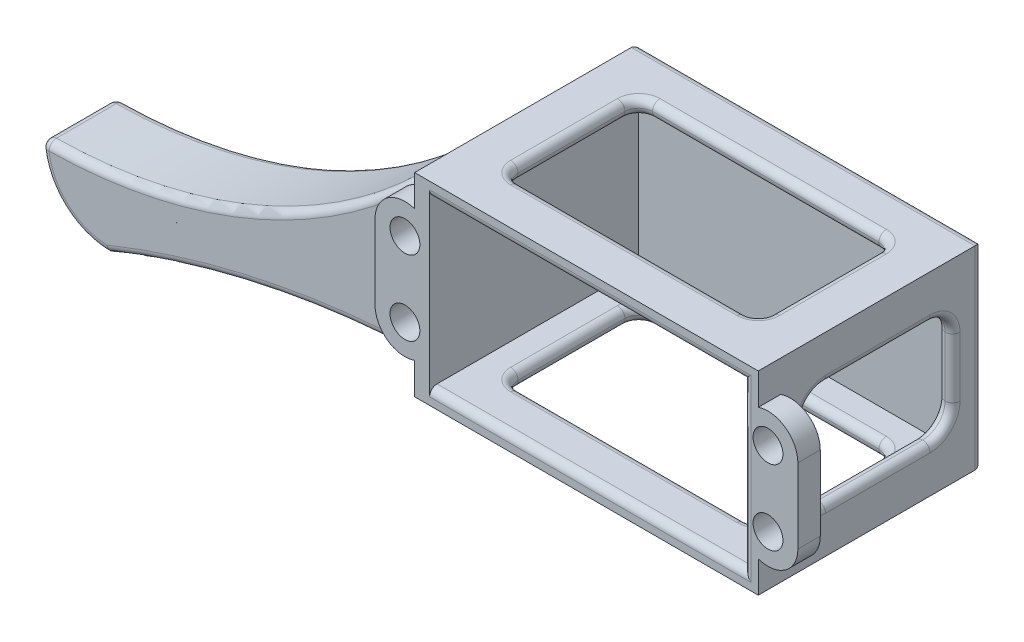
SolidWorks part; units mm, degrees
other "Markup1"
sketch "Sketch15" plane through (31.9332, 19.9963, 30) normal (0.1157, 0.1665, 0.9792) x (0.2474, -0.9596, 0.1339)
other "Markup2"
sketch "Sketch16" plane through (-78, 19.9963, 30) normal (-0.6723, 0.4833, 0.5608) x (0.1241, -0.6733, 0.7289)
material "Custom Plastic"
ref_plane "Front Plane" through (0, 0, 0) normal (0, 0, 1) x (1, 0, 0)
ref_plane "Top Plane" through (0, 0, 0) normal (0, 1, 0) x (1, 0, 0)
ref_plane "Right Plane" through (0, 0, 0) normal (1, 0, 0) x (0, 0, -1)
sketch "Sketch1" plane through (0, 0, 0) normal (0, 0, 1) x (1, 0, 0)
  line L0 (-23, 13) -> (-23, -13)
  line L1 (-20, 10) -> (20, 10) construction
  line L2 (-20, 10) -> (-20, -10) construction
  line L3 (-20, -10) -> (20, -10) construction
  line L4 (20, 10) -> (20, -10) construction
  line L5 (-20, 10) -> (20, -10) construction
  line L6 (-20, -10) -> (20, 10) construction
  line L7 (-23, -13) -> (23, -13)
  line L8 (23, 13) -> (23, -13)
  line L9 (-23, 13) -> (23, 13)
  point P0 (0, 0)
  dimension "D1" = 40
  dimension "D2" = 20
  dimension "D3" = 3
extrude "Boss-Extrude3" add sketch "Sketch1" along normal blind 30
shell "Shell1" thickness 2 removed face at (0, 0, 30)
sketch "Sketch2" plane through (0, 0, 30) normal (0, 0, 1) x (1, 0, 0)
  line L0 (0, 5) -> (0, -5) construction
  line L1 (-21, 11) -> (21, 11) construction
  line L2 (-21, 11) -> (-21, -11) construction
  line L3 (-21, -11) -> (21, -11) construction
  line L4 (21, 11) -> (21, -11) construction
  line L5 (-24.3, 5) -> (24.3, 5) construction
  line L6 (-24.3, 5) -> (-24.3, -5) construction
  line L7 (-24.3, -5) -> (24.3, -5) construction
  line L8 (24.3, 5) -> (24.3, -5) construction
  line L9 (-24.3, 5) -> (24.3, -5) construction
  line L10 (-24.3, -5) -> (24.3, 5) construction
  line L11 (-24.3, 0) -> (24.3, 0) construction
  line L13 (-28.3, 9) -> (28.3, 9)
  line L14 (-28.3, 9) -> (-28.3, -9)
  line L15 (-28.3, -9) -> (28.3, -9)
  line L16 (28.3, 9) -> (28.3, -9)
  line L17 (-28.3, 9) -> (28.3, -9) construction
  line L18 (-28.3, -9) -> (28.3, 9) construction
  circle A0 centre (-24.3, 5) radius 2
  circle A1 centre (24.3, 5) radius 2
  circle A2 centre (24.3, -5) radius 2
  circle A3 centre (-24.3, -5) radius 2
  circle A4 centre (-24.3, 5) radius 4
  circle A5 centre (-24.3, -5) radius 4
  circle A6 centre (24.3, 5) radius 4
  circle A7 centre (24.3, -5) radius 4
  point P6 (0, 0)
  point P28 (0, 0)
  line M7 (-23, 13) -> (-23, -13)
  line M9 (23, -13) -> (23, 13)
  dimension "D3" = 4
  dimension "D1" = 10
  dimension "D2" = 48.6
  dimension "D4" = 2
  dimension "D5" = 2
  dimension "D6" = 2
  dimension "D7" = 2
sketch "Sketch4" plane through (0, 0, 0) normal (0, 0, 1) x (1, 0, 0)
  line L0 (0, 5) -> (0, -5) construction
  line L1 (-20, 10) -> (20, 10) construction
  line L2 (-20, 10) -> (-20, -10) construction
  line L3 (-20, -10) -> (20, -10) construction
  line L4 (20, 10) -> (20, -10) construction
  line L5 (-24.3, 5) -> (24.3, 5) construction
  line L6 (-24.3, 5) -> (-24.3, -5) construction
  line L7 (-24.3, -5) -> (24.3, -5) construction
  line L8 (24.3, 5) -> (24.3, -5) construction
  line L9 (-24.3, 5) -> (24.3, -5) construction
  line L10 (-24.3, -5) -> (24.3, 5) construction
  line L11 (-24.3, 0) -> (24.3, 0) construction
  line L13 (-28.3, 9) -> (28.3, 9)
  line L14 (-28.3, 9) -> (-28.3, -9)
  line L15 (-28.3, -9) -> (28.3, -9)
  line L16 (28.3, 9) -> (28.3, -9)
  line L17 (-28.3, 9) -> (28.3, -9) construction
  line L18 (-28.3, -9) -> (28.3, 9) construction
  circle A0 centre (-24.3, 5) radius 2
  circle A1 centre (24.3, 5) radius 2
  circle A2 centre (24.3, -5) radius 2
  circle A3 centre (-24.3, -5) radius 2
  circle A4 centre (-24.3, 5) radius 4
  circle A5 centre (-24.3, -5) radius 4
  circle A6 centre (24.3, 5) radius 4
  circle A7 centre (24.3, -5) radius 4
  point P6 (0, 0)
  point P28 (0, 0)
  dimension "D3" = 4
  dimension "D1" = 10
  dimension "D2" = 48.6
  dimension "D4" = 2
  dimension "D5" = 2
  dimension "D6" = 2
  dimension "D7" = 2
extrude "Cut-Extrude2" cut sketch "Sketch4" along normal blind 17 from offset 25 contours A1 | A2 | A0 | A3 region at (-24.3, 5, 0) region at (24.3, 5, 0) region at (24.3, -5, 0) region at (-24.3, -5, 0)
extrude "Boss-Extrude4" add sketch "Sketch2" against normal blind 3 contours A6 A1 M9 | A7 L16 A6 M9 | A7 A2 M9 | A4 A0 M7 | L14 A5 A4 M7 | A5 A3 M7 region at (-23.6568, 8.8507, 30) region at (-26.3088, 0, 30) region at (-26.568, -1.8223, 30) region at (27.0606, 7.7606, 30) region at (26.3088, 0, 30) region at (27.0606, -7.7606, 30)
sketch "Sketch6" plane through (0, 13, 0) normal (0, 1, 0) x (1, 0, 0)
  line L0 (-23, -30) -> (-23, 0)
  line L1 (-23, 0) -> (23, 0)
  line L2 (23, 0) -> (23, -30)
  line L3 (23, -30) -> (23, 0) construction
  line L4 (23, -30) -> (-23, -30) construction
  line L5 (23, -30) -> (-23, -30)
  line L18 (17, -6) -> (-17, -6)
  line L19 (-17, -6) -> (-17, -24)
  line L20 (-17, -24) -> (17, -24)
  line L21 (17, -24) -> (17, -6)
  line L22 (15.1518, -6) -> (-15.1518, -6)
  line L23 (-17, -7.8482) -> (-17, -22.1518)
  line L24 (-15.1518, -24) -> (15.1518, -24)
  line L25 (17, -22.1518) -> (17, -7.8482)
  arc A0 (-15.1518, -6) -> (-17, -7.8482) centre (-15.1518, -7.8482) ccw
  arc A1 (-15.1518, -24) -> (-17, -22.1518) centre (-15.1518, -22.1518) cw
  arc A2 (15.1518, -24) -> (17, -22.1518) centre (15.1518, -22.1518) ccw
  arc A3 (17, -7.8482) -> (15.1518, -6) centre (15.1518, -7.8482) ccw
  dimension "D2" = 1.8482
  dimension "D1" = 6
sketch "Sketch9" plane through (0, 0, 0) normal (0, 0, 1) x (1, 0, 0)
  line L0 (0, 5) -> (0, -5) construction
  line L1 (-20, 10) -> (20, 10) construction
  line L2 (-20, 10) -> (-20, -10) construction
  line L3 (-20, -10) -> (20, -10) construction
  line L4 (20, 10) -> (20, -10) construction
  line L5 (-24.3, 5) -> (24.3, 5) construction
  line L6 (-24.3, 5) -> (-24.3, -5) construction
  line L7 (-24.3, -5) -> (24.3, -5) construction
  line L8 (24.3, 5) -> (24.3, -5) construction
  line L9 (-24.3, 5) -> (24.3, -5) construction
  line L10 (-24.3, -5) -> (24.3, 5) construction
  line L11 (-24.3, 0) -> (24.3, 0) construction
  line L12 (-24.3, 5) -> (-24.3, -5)
  line L13 (-28.3, 9) -> (28.3, 9)
  line L14 (-28.3, 9) -> (-28.3, -9)
  line L15 (-28.3, -9) -> (28.3, -9)
  line L16 (28.3, 9) -> (28.3, -9)
  line L17 (-28.3, 9) -> (28.3, -9) construction
  line L18 (-28.3, -9) -> (28.3, 9) construction
  line L19 (-24.3, 5) -> (10.5, 5)
  line L20 (-24.3, -5) -> (10.5, -5)
  line L21 (10.5, 5) -> (10.5, -5)
  circle A0 centre (-24.3, 5) radius 2
  circle A1 centre (24.3, 5) radius 2
  circle A2 centre (24.3, -5) radius 2
  circle A3 centre (-24.3, -5) radius 2
  circle A4 centre (-24.3, 5) radius 4
  circle A5 centre (-24.3, -5) radius 4
  circle A6 centre (24.3, 5) radius 4
  circle A7 centre (24.3, -5) radius 4
  circle A8 centre (10.5, 0) radius 4.5
  point P6 (0, 0)
  point P28 (0, 0)
  dimension "D3" = 4
  dimension "D9" = 9
  dimension "D1" = 10
  dimension "D2" = 48.6
  dimension "D8" = 34.8
  dimension "D4" = 2
  dimension "D5" = 2
  dimension "D6" = 2
  dimension "D7" = 2
extrude "Boss-Extrude16" add sketch "Sketch9" against normal blind 5 contours L21 A8 | L21 A8 region at (12.4099, 0, 0) region at (8.5901, 0, 0)
sketch "Sketch14" plane through (0, 0, 0) normal (0, 0, -1) x (-1, 0, 0)
  line L0 (69, 39) -> (69, -13)
  line L1 (-23, 13) -> (69, 13)
  line L2 (-23, 39) -> (-23, -13)
  line L3 (-23, -13) -> (69, -13) construction
  line L4 (23, 39) -> (23, -13)
  line L5 (-115, 39) -> (69, 39)
  line L6 (-69, 39) -> (-69, -65)
  line L7 (-23, 13) -> (-115, 13) construction
  line L8 (-115, 39) -> (-115, -65)
  line L9 (-23, -13) -> (-115, -13)
  line L10 (-23, -39) -> (-115, -39)
  line L11 (-23, -39) -> (161, -39)
  line L12 (23, -65) -> (23, -13)
  line L13 (-115, -65) -> (69, -65)
  line L14 (69, -65) -> (69, -13)
  line L15 (-23, -65) -> (-23, -13)
  line L16 (161, 13) -> (69, 13)
  line L17 (161, -13) -> (69, -13) construction
  line L18 (115, 39) -> (115, -13)
  line L19 (115, -65) -> (115, -13)
  line L20 (-14, 13) -> (-14, 22)
  line L21 (69, -13) -> (78, -13) construction
  line L22 (69, -13) -> (69, -22)
  line L23 (69, -22) -> (78, -22)
  line L24 (78, -13) -> (78, -22)
  line L25 (-14, 13) -> (-32, 13) construction
  line L26 (-23, 13) -> (-23, 22)
  line L27 (-14, 22) -> (-32, 22)
  line L28 (-32, 13) -> (-32, 22)
  line L30 (-23, 6.5199) -> (-32, 6.5199)
  line L31 (-23, 6.5199) -> (-23, 13)
  line L32 (-23, 13) -> (-32, 13)
  line L33 (-32, 6.5199) -> (-32, 13)
  line L34 (-23, 6.5199) -> (-21, 6.5199)
  line L35 (-23, 6.5199) -> (-23, 13)
  line L36 (-23, 13) -> (-21, 13)
  line L37 (-21, 6.5199) -> (-21, 13)
  arc A0 (23, -13) -> (69, -22) centre (23, -135.0556) cw
  arc A1 (69, -22) -> (78, -13) centre (69, -13) ccw
  arc A2 (78, -13) -> (23, 13) centre (78, 58.1731) cw
  arc A3 (-14, 13) -> (-30.0176, 19.6985) centre (-14, 35.5) cw
  arc A4 (-31.7134, 18.8176) -> (-29.7214, 13.2831) centre (-14.187, 22) ccw
  arc A5 (-31.9242, 7.6449) -> (-29.85, 12.125) centre (-23.6186, 6.5199) cw
  arc A6 (-23, 14.8784) -> (-30.8725, 6.5125) centre (-31.3814, 14.8784) cw
  arc A7 (-30.0176, 19.6985) -> (-31.7134, 18.8176) centre (-30.7295, 18.9963) ccw
  arc A8 (-29.85, 12.125) -> (-29.7214, 13.2831) centre (-30.5935, 12.7937) ccw
  arc A9 (-31.9242, 7.6449) -> (-30.8725, 6.5125) centre (-30.9332, 7.5106) ccw
  arc A10 (-29.7214, 13.2831) -> (-23, 6.5199) centre (-14.187, 22) ccw
  arc A11 (78, -16) -> (20.6817, 11.0959) centre (78, 58.1731) cw
  arc A12 (23, -10) -> (70.1306, -19.2212) centre (23, -135.0556) cw
  arc A13 (69, -19) -> (75, -13) centre (69, -13) ccw construction
  spline S0 degree 3 poles (59.5435, -15.4585) (63.9567, -16.6758) (61.1597, -13.9287) (59.5435, -13.667) knots 0 0 0 0 1 1 1 1
  point P9 (23, 13)
  point P18 (-69, -13)
  point P25 (69, -39)
  point P30 (78, -13)
  line M29 (23, -13) -> (23, 13)
  dimension "D5" = 1
  dimension "D1" = 55
  dimension "D2" = 9
  dimension "D3" = 9
  dimension "D4" = 9
  dimension "D6" = 2
  dimension "D7" = 3
extrude "Boss-Extrude18" add sketch "Sketch14" against normal blind 10 from offset 15 contours A12 A0 L14 M29 | S0 A12 L22 A11 | A1 A11 L22 L14 | A11 A1 A2 L0 L22 | S0 A11 L22 L0 A2 L4 | A12 S0 A11 L4 region at (-73.4109, -14.2953, 0) region at (-68.4591, -12.7143, 0) region at (-34.3258, -5.7975, 0) region at (-72.3453, -18.3731, 0) region at (-65.521, -16.1833, 0) region at (-46.2831, -14.4757, 0) offset against normal yes
extrude "Cut-Extrude5" cut sketch "Sketch6" against normal through all both and the other way through all contours A3 L25 A2 L24 A1 L23 A0 L22
fillet "Fillet50" radius 1 46 edges at (16.4587, 13, 6.5413) (17, 13, 15) (16.4587, 13, 23.4587) (0, 13, 24) (-16.4587, 13, 23.4587) (-17, 13, 15) (-16.4587, 13, 6.5413) (-16.4587, 11, 6.5413) (-17, 11, 15) (-16.4587, 11, 23.4587) (0, 11, 24) (16.4587, 11, 23.4587) (17, 11, 15) (16.4587, 11, 6.5413) (16.4587, -13, 6.5413) (17, -13, 15) (16.4587, -13, 23.4587) (0, -13, 24) (-16.4587, -13, 23.4587) (-17, -13, 15) (-16.4587, -13, 6.5413) (16.4587, -11, 6.5413) (17, -11, 15) (16.4587, -11, 23.4587) (0, -11, 24) (-16.4587, -11, 23.4587) (-17, -11, 15) (-16.4587, -11, 6.5413) (-23, 0, 0) (0, -13, 0) (23, 0, 0) (0, 13, 0) (0, 13, 6) (0, 11, 6) (0, -13, 6) (0, -11, 6) (-75.364, -19.364, 25) (-46.4361, -15.2711, 25) (-75.364, -19.364, 15) (-78, -13, 20) (-47.5821, -6.1725, 15) (-46.4361, -15.2711, 15) (-47.5821, -6.1725, 25) (0, -11, 30) (0, 11, 30) (21, 0, 30)
sketch "Sketch17" plane through (23, 0, 0) normal (1, 0, 0) x (0, 0, -1)
  line L0 (-24, 4) -> (-24, -4)
  line L1 (-30, 13) -> (-1, 13)
  line L2 (-30, 13) -> (-30, -13)
  line L3 (-30, -13) -> (-1, -13)
  line L4 (-1, 13) -> (-1, -13)
  line L5 (-21, -7) -> (-10, -7)
  line L6 (-7, 4) -> (-7, -4)
  line L7 (-21, 7) -> (-10, 7)
  line L8 (-24, -7) -> (-7, -7) construction
  line L9 (-24, 7) -> (-24, -7) construction
  line L10 (-7, 7) -> (-7, -7) construction
  line L11 (-24, 7) -> (-7, 7) construction
  line L12 (-21, 4) -> (-21, -4)
  line L13 (-18, -7) -> (-7, -7)
  line L14 (-4, 4) -> (-4, -4)
  line L15 (-18, 7) -> (-7, 7)
  arc A0 (-21, -7) -> (-24, -4) centre (-21, -4) cw
  arc A1 (-7, -4) -> (-10, -7) centre (-10, -4) cw
  arc A2 (-7, 4) -> (-10, 7) centre (-10, 4) ccw
  arc A3 (-21, 7) -> (-24, 4) centre (-21, 4) ccw
  arc A4 (-18, 7) -> (-21, 4) centre (-18, 4) ccw
  arc A5 (-18, -7) -> (-21, -4) centre (-18, -4) cw
  arc A6 (-4, -4) -> (-7, -7) centre (-7, -4) cw
  arc A7 (-4, 4) -> (-7, 7) centre (-7, 4) ccw
  dimension "D2" = 3
  dimension "D1" = 6
  dimension "D3" = 2
extrude "Cut-Extrude6" cut sketch "Sketch17" against normal blind 10 contours A3 L7 A2 L6 A1 L5 A0 L0 | L12 A5 L13 A6 L14 A7 L15 A4
fillet "Fillet51" radius 1 16 edges at (21, -6.1213, 4.8787) (21, -7, 14) (21, -6.1213, 23.1213) (21, 0, 24) (21, 6.1213, 23.1213) (21, 7, 14) (21, 6.1213, 4.8787) (23, 6.1213, 4.8787) (23, 7, 14) (23, 6.1213, 23.1213) (23, 0, 24) (23, -6.1213, 23.1213) (23, -7, 14) (23, -6.1213, 4.8787) (21, 0, 4) (23, 0, 4)
